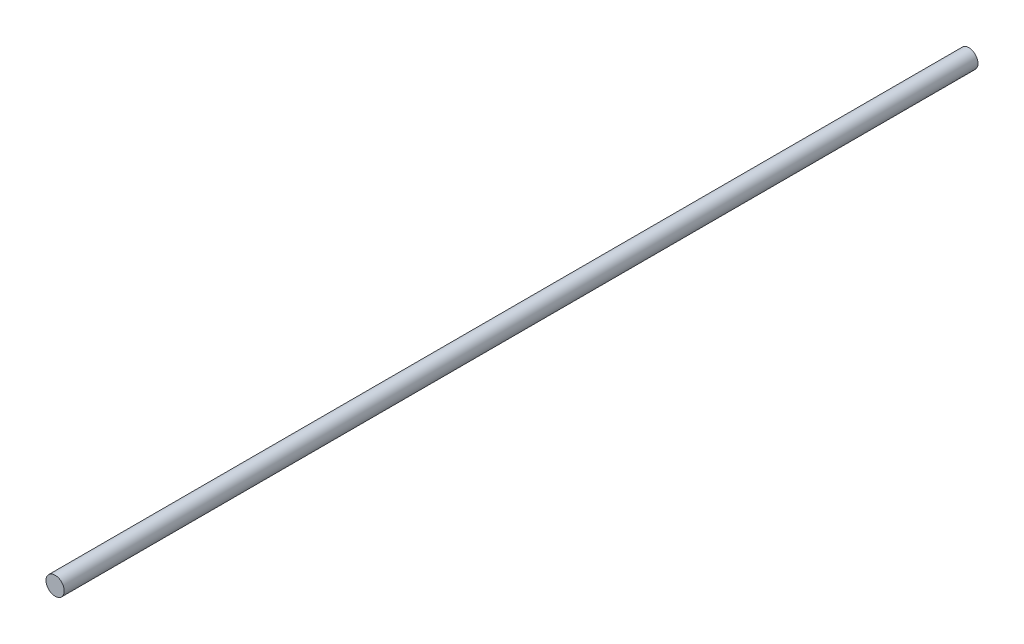
SolidWorks part; units mm, degrees
ref_plane "Front Plane" through (0, 0, 0) normal (0, 0, 1) x (1, 0, 0)
ref_plane "Top Plane" through (0, 0, 0) normal (0, 1, 0) x (1, 0, 0)
ref_plane "Right Plane" through (0, 0, 0) normal (1, 0, 0) x (0, 0, -1)
sketch "Sketch1" plane through (0, 0, 0) normal (0, 0, 1) x (1, 0, 0)
  circle A0 centre (0, 0) radius 4
  dimension "D1" = 8
extrude "Boss-Extrude1" add sketch "Sketch1" against normal blind 400
ref_axis "Axis1" through (0, 0, -400) along (0, 0, 1)
ref_plane "Plane1" through (0, 0, -200) normal (0, 0, 1) x (1, 0, 0)
